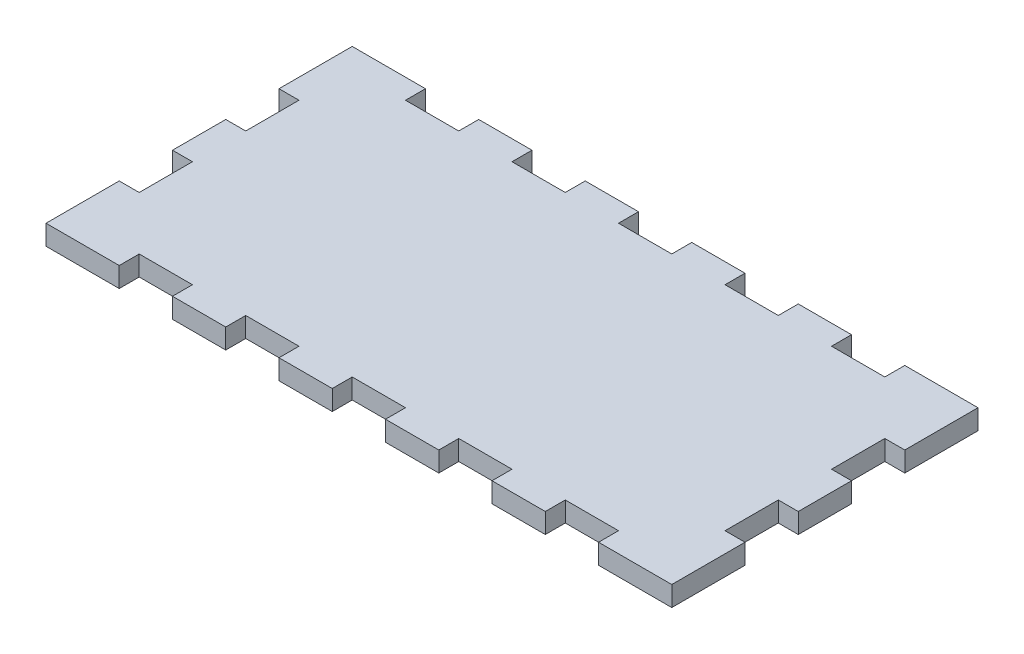
SolidWorks part; units mm, degrees
ref_plane "Front Plane" through (0, 0, 0) normal (0, 0, 1) x (1, 0, 0)
ref_plane "Top Plane" through (0, 0, 0) normal (0, 1, 0) x (1, 0, 0)
ref_plane "Right Plane" through (0, 0, 0) normal (1, 0, 0) x (0, 0, -1)
sketch "Sketch2" plane through (0, 0, 0) normal (0, 1, 0) x (1, 0, 0)
  line L1 (139.7, -63.5) -> (-139.7, -63.5)
  line L2 (139.7, -63.5) -> (139.7, 63.5)
  line L3 (139.7, 63.5) -> (-139.7, 63.5)
  line L4 (-139.7, -63.5) -> (-139.7, 63.5)
  line L5 (139.7, -63.5) -> (-139.7, 63.5) construction
  line L6 (139.7, 63.5) -> (-139.7, -63.5) construction
  point P0 (0, 0)
  dimension "D1" = 279.4
  dimension "D2" = 127
extrude "Boss-Extrude1" add sketch "Sketch2" along normal blind 9.525
sketch "Sketch3" plane through (0, 0, 63.5) normal (0, 0, 1) x (1, 0, 0)
  line L0 (-139.7, 9.525) -> (139.7, 9.525) construction
  line L1 (-139.7, 0) -> (-114.3, 0)
  line L2 (-139.7, 0) -> (-139.7, 9.525)
  line L3 (-139.7, 9.525) -> (-114.3, 9.525)
  line L4 (-114.3, 0) -> (-114.3, 9.525)
  dimension "D1" = 25.4
extrude "Boss-Extrude2" add sketch "Sketch3" along normal blind 9.525
pattern_linear "LPattern1" count 6 spacing 50.8 along (1, 0, 0) of "Boss-Extrude2"
mirror "Mirror1" about plane through (0, 0, 0) normal (0, 0, 1) of "LPattern1"
sketch "Sketch4" plane through (139.7, 0, 0) normal (1, 0, 0) x (0, 0, -1)
  line L0 (-73.025, 0) -> (73.025, 0) construction
  line L1 (-63.5, 0) -> (-38.1, 0)
  line L2 (-63.5, 0) -> (-63.5, 9.525)
  line L3 (-63.5, 9.525) -> (-38.1, 9.525)
  line L4 (-38.1, 0) -> (-38.1, 9.525)
  line L5 (-73.025, 9.525) -> (73.025, 9.525) construction
  line L6 (-73.025, 0) -> (-73.025, 9.525) construction
  dimension "D1" = 9.525
  dimension "D2" = 25.4
extrude "Boss-Extrude3" add sketch "Sketch4" along normal blind 9.525
pattern_linear "LPattern2" count 3 spacing 50.8 along (0, 0, -1) of "Boss-Extrude3"
mirror "Mirror2" about plane through (0, 0, 0) normal (1, 0, 0) of "LPattern2"
sketch "Sketch6" plane through (0, 0, 63.5) normal (0, 0, 1) x (1, 0, 0)
  line L1 (149.225, 9.525) -> (139.7, 9.525)
  line L2 (149.225, 9.525) -> (149.225, 0)
  line L3 (149.225, 0) -> (139.7, 0)
  line L4 (139.7, 9.525) -> (139.7, 0)
extrude "Boss-Extrude4" add sketch "Sketch6" along normal blind 9.525
mirror "Mirror3" about plane through (0, 0, 0) normal (1, 0, 0) of "Boss-Extrude4"
mirror "Mirror4" about plane through (0, 0, 0) normal (0, 0, 1) of "Mirror3"
sketch "Sketch7" plane through (0, 9.525, 0) normal (0, 1, 0) x (1, 0, 0)
  circle A0 centre (-29.2864, 23.8119) radius 0.032
  circle A1 centre (-23.072, 14.7922) radius 0.1056
  circle A2 centre (27.5, 22.9863) radius 2
  circle A3 centre (22.5, 12.9863) radius 2
extrude "Cut-Extrude1" [suppressed] cut sketch "Sketch7" against normal through all
sketch "Sketch8" plane through (0, 9.525, 0) normal (0, 1, 0) x (1, 0, 0)
  circle A0 centre (-25.974, 23.4033) radius 0.0509
  circle A1 centre (-24.0521, 14.3728) radius 0.0812
  circle A2 centre (-27.5, -1.2321) radius 2
  circle A3 centre (-22.5, -11.2321) radius 2
extrude "Cut-Extrude3" [suppressed] cut sketch "Sketch8" against normal through all contours A2 A0 | A3
sketch "Sketch9" [suppressed] plane through (0, 0, 0) normal (0, -1, 0) x (1, 0, 0)
  circle A0 centre (-22.5, -12.9863) radius 3.81
  circle A1 centre (-27.5, -22.9863) radius 3.81
  circle A2 centre (22.5, -12.9863) radius 3.81
  circle A3 centre (27.5, -22.9863) radius 3.81
  dimension "D1" = 7.62
  dimension "D2" = 7.62
  dimension "D3" = 7.62
  dimension "D4" = 7.62
extrude "Cut-Extrude4" [suppressed] cut sketch "Sketch9" against normal blind 4.7625
